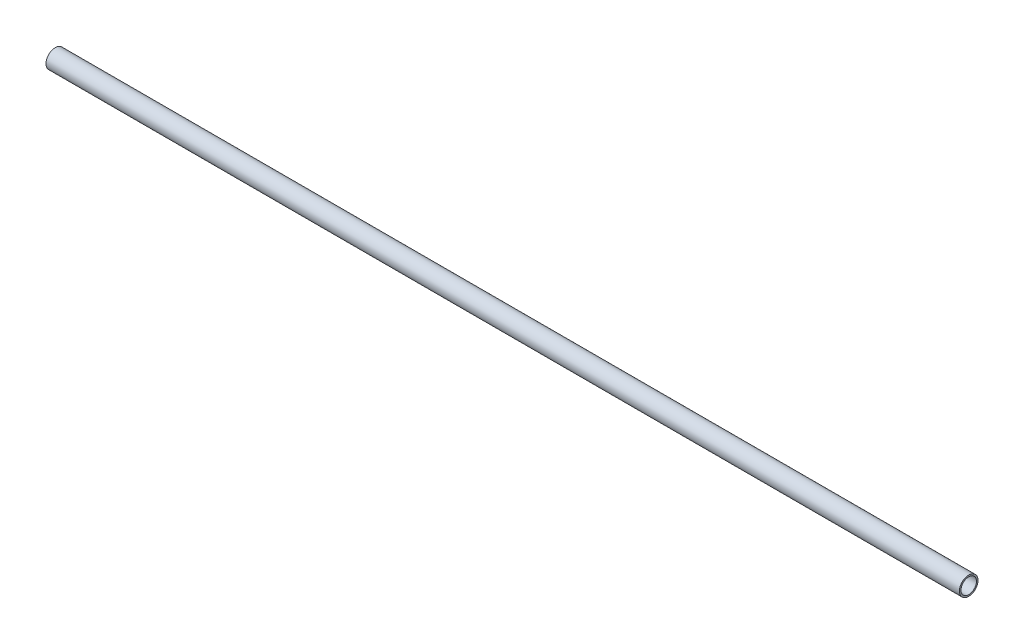
SolidWorks part; units mm, degrees
ref_plane "Front Plane" through (0, 0, 0) normal (0, 0, 1) x (1, 0, 0)
ref_plane "Top Plane" through (0, 0, 0) normal (0, 1, 0) x (1, 0, 0)
ref_plane "Right Plane" through (0, 0, 0) normal (1, 0, 0) x (0, 0, -1)
ref_axis "Axis1" through (-4.5, 0, 0) along (1, 0, 0)
sketch "Sketch1" plane through (0, 0, 0) normal (1, 0, 0) x (0, 0, -1)
  circle A0 centre (0, 0) radius 0.762
  circle A1 centre (0, 0) radius 0.9144
  dimension "D1" = 1.524
  dimension "D2" = 1.8288
extrude "Boss-Extrude1" add sketch "Sketch1" along normal blind 90
sketch "Sketch2" plane through (0, 0, 0) normal (-1, 0, 0) x (0, 0, 1)
  line L0 (0, 0) -> (0, 0.6106) construction
  line L2 (-0.304, 0.6106) -> (-0.304, 1.0992)
  line L3 (-0.304, 1.0992) -> (0.304, 1.0992)
  line L4 (0.304, 1.0992) -> (0.304, 0.6106)
  arc A0 (-0.304, 0.6106) -> (0.304, 0.6106) centre (0, 0.6106) ccw
  dimension "D1" = 0.608
extrude "Cut-Extrude1" [suppressed] cut sketch "Sketch2" against normal blind 1
sketch "Sketch3" plane through (0, 0, 0) normal (0, 0, 1) x (1, 0, 0)
  circle A0 centre (0.7986, 0) radius 0.3969
  dimension "D1" = 0.7937
extrude "Cut-Extrude2" cut sketch "Sketch3" against normal blind 10
equation "\"Do\"=8.5mm"
equation "\"Lo\"=10"
equation "\"screw_diam\" = 3.5mm"
equation "\"wheel_Do\"=12.5mm"
equation "\"wheel_thickness\"=4mm"
equation "\"Collet_diameter\"=4.3"
equation "\"clearance\"= 0.5mm"
equation "\"handle_body_width\" = 10mm"
equation "\"finger_diameter\"=35"
equation "\"collet_lid_diameter\"=10"
equation "\"screw_cap_diam\"=5.15"
equation "\"handle_thickness\"=12.5mm"
equation "\"post_hole_diam\"=2"
equation "\"roll_rod_diam\"= 6.5 "
equation "\"roll_rod_length\"=6.6"
equation "\"disc_diam\"=5"
equation "\"disc_width\"=1.5"
equation "\"arm_width\"=5"
equation "\"arm_thickness\"=4.5"
equation "\"wheel_total_diam\"=30"
equation "\"spring_diam\"=4.1"
equation "\"collet_length\" = 18.75mm"
equation "\"tip_length\" = 40mm"
equation "\"cable_tube_OD\"=0.508"
equation "\"D1@Sketch2\"=\"cable_tube_OD\"+0.1"
